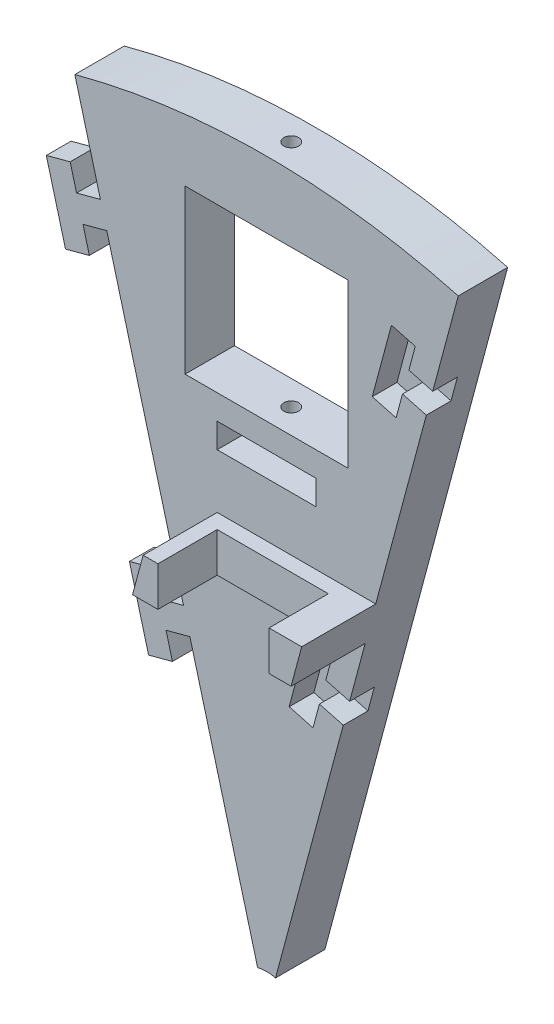
SolidWorks part; units mm, degrees
ref_plane "Front Plane" through (0, 0, 0) normal (0, 0, 1) x (1, 0, 0)
ref_plane "Top Plane" through (0, 0, 0) normal (0, 1, 0) x (1, 0, 0)
ref_plane "Right Plane" through (0, 0, 0) normal (1, 0, 0) x (0, 0, -1)
sketch "Sketch1" plane through (0, 0, 0) normal (0, 0, 1) x (1, 0, 0)
  line L0 (0, 0) -> (103.5, 0) construction
  line L1 (37.4606, 97.8836) -> (66.0394, 81.3836)
  line L2 (-16.5, 103.5) -> (16.5, 103.5)
  line L3 (-16.5, 103.5) -> (-16.5, 136.5)
  line L4 (-16.5, 136.5) -> (16.5, 136.5)
  line L5 (16.5, 103.5) -> (16.5, 136.5)
  line L6 (-16.5, 103.5) -> (16.5, 136.5) construction
  line L7 (-16.5, 136.5) -> (16.5, 103.5) construction
  line L8 (37.4606, 97.8836) -> (53.9606, 126.4625)
  line L9 (53.9606, 126.4625) -> (82.5394, 109.9625)
  line L10 (66.0394, 81.3836) -> (82.5394, 109.9625)
  line L11 (81.3836, 66.0394) -> (97.8836, 37.4606)
  line L12 (81.3836, 66.0394) -> (109.9625, 82.5394)
  line L13 (109.9625, 82.5394) -> (126.4625, 53.9606)
  line L14 (97.8836, 37.4606) -> (126.4625, 53.9606)
  line L15 (103.5, 16.5) -> (103.5, -16.5)
  line L16 (103.5, 16.5) -> (136.5, 16.5)
  line L17 (136.5, 16.5) -> (136.5, -16.5)
  line L18 (103.5, -16.5) -> (136.5, -16.5)
  line L19 (97.8836, -37.4606) -> (81.3836, -66.0394)
  line L20 (97.8836, -37.4606) -> (126.4625, -53.9606)
  line L21 (126.4625, -53.9606) -> (109.9625, -82.5394)
  line L22 (81.3836, -66.0394) -> (109.9625, -82.5394)
  line L23 (66.0394, -81.3836) -> (37.4606, -97.8836)
  line L24 (66.0394, -81.3836) -> (82.5394, -109.9625)
  line L25 (82.5394, -109.9625) -> (53.9606, -126.4625)
  line L26 (37.4606, -97.8836) -> (53.9606, -126.4625)
  line L27 (16.5, -103.5) -> (-16.5, -103.5)
  line L28 (16.5, -103.5) -> (16.5, -136.5)
  line L29 (16.5, -136.5) -> (-16.5, -136.5)
  line L30 (-16.5, -103.5) -> (-16.5, -136.5)
  line L31 (-37.4606, -97.8836) -> (-66.0394, -81.3836)
  line L32 (-37.4606, -97.8836) -> (-53.9606, -126.4625)
  line L33 (-53.9606, -126.4625) -> (-82.5394, -109.9625)
  line L34 (-66.0394, -81.3836) -> (-82.5394, -109.9625)
  line L35 (-81.3836, -66.0394) -> (-97.8836, -37.4606)
  line L36 (-81.3836, -66.0394) -> (-109.9625, -82.5394)
  line L37 (-109.9625, -82.5394) -> (-126.4625, -53.9606)
  line L38 (-97.8836, -37.4606) -> (-126.4625, -53.9606)
  line L39 (-103.5, -16.5) -> (-103.5, 16.5)
  line L40 (-103.5, -16.5) -> (-136.5, -16.5)
  line L41 (-136.5, -16.5) -> (-136.5, 16.5)
  line L42 (-103.5, 16.5) -> (-136.5, 16.5)
  line L43 (-97.8836, 37.4606) -> (-81.3836, 66.0394)
  line L44 (-97.8836, 37.4606) -> (-126.4625, 53.9606)
  line L45 (-126.4625, 53.9606) -> (-109.9625, 82.5394)
  line L46 (-81.3836, 66.0394) -> (-109.9625, 82.5394)
  line L47 (-66.0394, 81.3836) -> (-37.4606, 97.8836)
  line L48 (-66.0394, 81.3836) -> (-82.5394, 109.9625)
  line L49 (-82.5394, 109.9625) -> (-53.9606, 126.4625)
  line L50 (-37.4606, 97.8836) -> (-53.9606, 126.4625)
  line L51 (0, 103.5) -> (0, 0) construction
  line L52 (0, 0) -> (0, -103.5) construction
  circle A0 centre (0, 0) radius 150
  point P4 (0, 120)
  point P56 (0, 0)
  dimension "D1" = 300
  dimension "D2" = 33
  dimension "D3" = 120
  dimension "D4" = 12
extrude "Boss-Extrude1" add sketch "Sketch1" along normal mid plane 10
ref_plane "Plane1" through (0, -150, 0) normal (0, -1, 0) x (-1, 0, 0)
sketch "Sketch4" plane through (0, -150, 0) normal (0, -1, 0) x (-1, 0, 0)
  circle A0 centre (0, 0) radius 1.5
  dimension "D1" = 3
extrude "Cut-Extrude1" cut sketch "Sketch4" against normal blind 55
pattern_circular "CirPattern1" count 12 every 30 about axis through (0, 0, 5) along (0, 0, -1) of "Cut-Extrude1" reverse direction yes
sketch "Sketch5" plane through (0, 0, -5) normal (0, 0, -1) x (-1, 0, 0)
  line L0 (0, 0) -> (0, 116.0721) construction
  line L1 (38.0897, 85.9734) -> (55.4103, 75.9734)
  line L2 (-10, 93.5) -> (10, 93.5)
  line L3 (-10, 93.5) -> (-10, 98.5)
  line L4 (-10, 98.5) -> (10, 98.5)
  line L5 (10, 93.5) -> (10, 98.5)
  line L6 (-10, 93.5) -> (10, 98.5) construction
  line L7 (-10, 98.5) -> (10, 93.5) construction
  line L8 (16.5, 103.5) -> (-16.5, 103.5) construction
  line L9 (38.0897, 85.9734) -> (40.5897, 90.3035)
  line L10 (40.5897, 90.3035) -> (57.9103, 80.3035)
  line L11 (55.4103, 75.9734) -> (57.9103, 80.3035)
  line L12 (75.9734, 55.4103) -> (85.9734, 38.0897)
  line L13 (75.9734, 55.4103) -> (80.3035, 57.9103)
  line L14 (80.3035, 57.9103) -> (90.3035, 40.5897)
  line L15 (85.9734, 38.0897) -> (90.3035, 40.5897)
  line L16 (93.5, 10) -> (93.5, -10)
  line L17 (93.5, 10) -> (98.5, 10)
  line L18 (98.5, 10) -> (98.5, -10)
  line L19 (93.5, -10) -> (98.5, -10)
  line L20 (85.9734, -38.0897) -> (75.9734, -55.4103)
  line L21 (85.9734, -38.0897) -> (90.3035, -40.5897)
  line L22 (90.3035, -40.5897) -> (80.3035, -57.9103)
  line L23 (75.9734, -55.4103) -> (80.3035, -57.9103)
  line L24 (55.4103, -75.9734) -> (38.0897, -85.9734)
  line L25 (55.4103, -75.9734) -> (57.9103, -80.3035)
  line L26 (57.9103, -80.3035) -> (40.5897, -90.3035)
  line L27 (38.0897, -85.9734) -> (40.5897, -90.3035)
  line L28 (10, -93.5) -> (-10, -93.5)
  line L29 (10, -93.5) -> (10, -98.5)
  line L30 (10, -98.5) -> (-10, -98.5)
  line L31 (-10, -93.5) -> (-10, -98.5)
  line L32 (-38.0897, -85.9734) -> (-55.4103, -75.9734)
  line L33 (-38.0897, -85.9734) -> (-40.5897, -90.3035)
  line L34 (-40.5897, -90.3035) -> (-57.9103, -80.3035)
  line L35 (-55.4103, -75.9734) -> (-57.9103, -80.3035)
  line L36 (-75.9734, -55.4103) -> (-85.9734, -38.0897)
  line L37 (-75.9734, -55.4103) -> (-80.3035, -57.9103)
  line L38 (-80.3035, -57.9103) -> (-90.3035, -40.5897)
  line L39 (-85.9734, -38.0897) -> (-90.3035, -40.5897)
  line L40 (-93.5, -10) -> (-93.5, 10)
  line L41 (-93.5, -10) -> (-98.5, -10)
  line L42 (-98.5, -10) -> (-98.5, 10)
  line L43 (-93.5, 10) -> (-98.5, 10)
  line L44 (-85.9734, 38.0897) -> (-75.9734, 55.4103)
  line L45 (-85.9734, 38.0897) -> (-90.3035, 40.5897)
  line L46 (-90.3035, 40.5897) -> (-80.3035, 57.9103)
  line L47 (-75.9734, 55.4103) -> (-80.3035, 57.9103)
  line L48 (-55.4103, 75.9734) -> (-38.0897, 85.9734)
  line L49 (-55.4103, 75.9734) -> (-57.9103, 80.3035)
  line L50 (-57.9103, 80.3035) -> (-40.5897, 90.3035)
  line L51 (-38.0897, 85.9734) -> (-40.5897, 90.3035)
  line L52 (-103.5, 16.5) -> (-103.5, -16.5) construction
  line L53 (-16.5, -103.5) -> (16.5, -103.5) construction
  point P1 (0, 96)
  point P57 (0, 0)
  dimension "D1" = 5
  dimension "D2" = 20
  dimension "D3" = 5
  dimension "D5" = 5
  dimension "D6" = 5
  dimension "D4" = 12
extrude "Cut-Extrude2" cut sketch "Sketch5" against normal up to next
sketch "Sketch6" plane through (0, 0, 5) normal (0, 0, 1) x (1, 0, 0)
  line L0 (0, 0) -> (-38.8229, 144.8889)
  line L1 (0, 0) -> (38.8229, 144.8889)
  line L2 (0, 175.6379) -> (0, 153.992) construction
  line L3 (-38.8229, 144.8889) -> (0, 144.8889)
  line L4 (0, 144.8889) -> (38.8229, 144.8889)
  circle A0 centre (0, 0) radius 150 construction
  arc A1 (-1.8117, 6.7615) -> (1.8117, 6.7615) centre (0, 0) cw
  circle A2 centre (0, 0) radius 150
  dimension "D2" = 7
  dimension "D1" = 30
extrude "Cut-Extrude3" cut sketch "Sketch6" against normal blind 10 contours L2 L0 A2 | L1 L2 A2 | A1 L2 L1 | L2 A1 L0 region at (0, -8.9874, 5) region at (0, 4.6135, 5)
sketch "Sketch7" plane through (0, 0, 5) normal (0, 0, 1) x (1, 0, 0)
  line L0 (-24.5878, 91.763) -> (-39.0277, 87.8938) construction
  line L1 (-1.8117, 6.7615) -> (-38.8229, 144.8889) construction
  line L2 (-1.8117, 6.7615) -> (-38.8229, 144.8889)
  line L3 (-35.8879, 114.617) -> (-37.182, 119.4466)
  line L4 (-37.182, 119.4466) -> (-32.3524, 120.7407)
  line L5 (30.0564, 131.7087) -> (25.2268, 133.0028)
  line L6 (25.2268, 133.0028) -> (21.3445, 118.5139)
  line L7 (28.7623, 126.8791) -> (30.0564, 131.7087)
  line L8 (-33.6465, 125.5704) -> (-38.4761, 124.2763)
  line L9 (-38.4761, 124.2763) -> (-39.7702, 129.1059)
  line L10 (-39.7702, 129.1059) -> (-44.5998, 127.8118)
  line L11 (-44.5998, 127.8118) -> (-40.7175, 113.3229)
  line L12 (33.5919, 125.585) -> (28.7623, 126.8791)
  line L13 (26.1741, 117.2198) -> (27.4682, 122.0494)
  line L14 (-40.7175, 113.3229) -> (-35.8879, 114.617)
  line L15 (21.3445, 118.5139) -> (26.1741, 117.2198)
  line L16 (27.4682, 122.0494) -> (32.2978, 120.7553)
  line L17 (0, 0.1091) -> (-35.8879, 114.617) construction
  line L18 (0, 0.1091) -> (26.1741, 117.2198) construction
  line L19 (-27.7766, 65.0266) -> (-22.947, 66.3207)
  line L20 (-22.947, 66.3207) -> (-21.6529, 61.4911)
  line L21 (-21.6529, 61.4911) -> (-16.8232, 62.7852)
  line L22 (-15.5291, 57.9555) -> (-20.3588, 56.6615)
  line L23 (-23.8943, 50.5377) -> (-27.7766, 65.0266)
  line L24 (-20.3588, 56.6615) -> (-19.0647, 51.8318)
  line L25 (-19.0647, 51.8318) -> (-23.8943, 50.5377)
  line L26 (8.4854, 70.3048) -> (13.315, 69.0107)
  line L27 (4.6031, 55.8159) -> (8.4854, 70.3048)
  line L28 (13.315, 69.0107) -> (12.0209, 64.1811)
  line L29 (12.0209, 64.1811) -> (16.8505, 62.887)
  line L30 (15.5564, 58.0574) -> (10.7268, 59.3514)
  line L31 (10.7268, 59.3514) -> (9.4327, 54.5218)
  line L32 (9.4327, 54.5218) -> (4.6031, 55.8159)
  line L33 (1.8117, 6.7615) -> (38.8229, 144.8889) construction
  point P7 (-38.3027, 113.97)
  point P44 (0.2036, 0)
  point P47 (0.2036, 0)
  line M9 (-38.8229, 144.8889) -> (-1.8117, 6.7615)
  dimension "D1" = 5
  dimension "D2" = 90
  dimension "D3" = 5
  dimension "D4" = 5
  dimension "D5" = 20
  dimension "D6" = 15
  dimension "D7" = 5
  dimension "D8" = 5
  dimension "D9" = 90
  dimension "D11" = 30
  dimension "D12" = 20
  dimension "D13" = 120
  dimension "D14" = 30
  dimension "D17" = 60
  dimension "D18" = 10
  dimension "D10" = 2
  dimension "D15" = 2
  dimension "D16" = 2
extrude "Boss-Extrude2" add sketch "Sketch7" against normal blind 5 contours L25 L24 L22 L21 L20 L19 L23 M9 | L11 L14 L3 L4 L2 L8 L9 L10 region at (-22.2132, 58.7527, 5) region at (-39.0365, 121.5379, 5)
sketch "Sketch9" plane through (0, 0, 5) normal (0, 0, 1) x (1, 0, 0)
  line L0 (-15.5291, 57.9555) -> (-20.3588, 56.6615) construction
  line L1 (-20.3588, 56.6615) -> (-19.0647, 51.8318) construction
  line L2 (-19.0647, 51.8318) -> (-23.8943, 50.5377) construction
  line L3 (-23.8943, 50.5377) -> (-27.7766, 65.0266) construction
  line L4 (-27.7766, 65.0266) -> (-22.947, 66.3207) construction
  line L5 (-21.6529, 61.4911) -> (-16.8232, 62.7852) construction
  line L6 (-37.182, 119.4466) -> (-32.3524, 120.7407) construction
  line L7 (-35.8879, 114.617) -> (-37.182, 119.4466) construction
  line L8 (-40.7175, 113.3229) -> (-35.8879, 114.617) construction
  line L9 (-44.5998, 127.8118) -> (-40.7175, 113.3229) construction
  line L10 (-39.7702, 129.1059) -> (-44.5998, 127.8118) construction
  line L11 (-38.4761, 124.2763) -> (-39.7702, 129.1059) construction
  line L12 (-33.6465, 125.5704) -> (-38.4761, 124.2763) construction
  line L13 (-15.5291, 57.9555) -> (-20.3588, 56.6615)
  line L14 (-20.3588, 56.6615) -> (-19.0647, 51.8318)
  line L15 (-19.0647, 51.8318) -> (-23.8943, 50.5377)
  line L16 (-23.8943, 50.5377) -> (-27.7766, 65.0266)
  line L17 (-27.7766, 65.0266) -> (-22.947, 66.3207)
  line L18 (-21.6529, 61.4911) -> (-16.8232, 62.7852)
  line L19 (-37.182, 119.4466) -> (-32.3524, 120.7407)
  line L20 (-35.8879, 114.617) -> (-37.182, 119.4466)
  line L21 (-40.7175, 113.3229) -> (-35.8879, 114.617)
  line L22 (-44.5998, 127.8118) -> (-40.7175, 113.3229)
  line L23 (-39.7702, 129.1059) -> (-44.5998, 127.8118)
  line L24 (-38.4761, 124.2763) -> (-39.7702, 129.1059)
  line L25 (-33.6465, 125.5704) -> (-38.4761, 124.2763)
  line L26 (33.6465, 125.5704) -> (28.8168, 126.8645)
  line L27 (30.1109, 131.6941) -> (25.2813, 132.9882)
  line L28 (27.5228, 122.0348) -> (32.3524, 120.7407)
  line L29 (26.2287, 117.2052) -> (27.5228, 122.0348)
  line L30 (21.399, 118.4993) -> (26.2287, 117.2052)
  line L31 (25.2813, 132.9882) -> (21.399, 118.4993)
  line L32 (28.8168, 126.8645) -> (30.1109, 131.6941)
  line L33 (15.5291, 57.9555) -> (10.6995, 59.2496)
  line L34 (10.6995, 59.2496) -> (9.4054, 54.42)
  line L35 (9.4054, 54.42) -> (4.5758, 55.7141)
  line L36 (4.5758, 55.7141) -> (8.4581, 70.203)
  line L37 (11.9936, 64.0793) -> (16.8232, 62.7852)
  line L38 (8.4581, 70.203) -> (13.2877, 68.9089)
  line L39 (0, 0) -> (-19.0647, 51.8318) construction
  line L40 (0, 0) -> (9.4054, 54.42) construction
  line L41 (-22.947, 66.3207) -> (-21.6529, 61.4911) construction
  line L42 (-22.947, 66.3207) -> (-21.6529, 61.4911)
  line L43 (13.2877, 68.9089) -> (11.9936, 64.0793)
  point P39 (0, 0)
  line M5 (1.8117, 6.7615) -> (38.8229, 144.8889)
  dimension "D2" = 30
  dimension "D1" = 2
  dimension "D3" = 2
extrude "Cut-Extrude4" cut sketch "Sketch9" against normal blind 5 contours L43 L38 L36 L35 L34 L33 L37 M5 | L26 L32 L27 L31 L30 L29 L28 M5 region at (26.9624, 124.7732, 5) region at (10.1392, 61.988, 5)
sketch "Sketch10" plane through (0, 0, 5) normal (0, 0, 1) x (1, 0, 0)
  line L0 (-10, 93.5) -> (-10, 98.5) construction
  line L1 (-10, 82.5) -> (-7, 82.5)
  line L3 (-10, 74.5) -> (-7, 74.5)
  line L4 (-7, 82.5) -> (-7, 74.5)
  line L5 (-10, 82.5) -> (-12.1436, 74.5)
  line L6 (-12.1436, 74.5) -> (-10, 74.5)
  line L7 (10, 93.5) -> (-10, 93.5) construction
  line L8 (16.8232, 62.7852) -> (32.3524, 120.7407) construction
  line L9 (15.5, 82.5) -> (22.1058, 82.5)
  line L10 (15.5, 82.5) -> (15.5, 74.5)
  line L11 (15.5, 74.5) -> (19.9622, 74.5)
  line L12 (22.1058, 82.5) -> (19.9622, 74.5)
  line L13 (16.8232, 62.7852) -> (32.3524, 120.7407)
  point P15 (0, 0)
  line M19 (16.8232, 62.7852) -> (32.3524, 120.7407)
  dimension "D1" = 3
  dimension "D2" = 11
  dimension "D3" = 22.5
  dimension "D4" = 3
  dimension "D5" = 8
  dimension "D6" = 8
  dimension "D7" = 75
extrude "Boss-Extrude3" add sketch "Sketch10" along normal blind 15 contours L4 L1 L3 | L10 L11 L9 M19 region at (-9.0829, 78.149, 5) region at (18.3016, 78.7582, 5)
sketch "Sketch11" plane through (0, 0, 5) normal (0, 0, 1) x (1, 0, 0)
  line L0 (-7, 82.5) -> (-7, 74.5) construction
  line L1 (-7, 82.5) -> (-7, 74.5)
  line L3 (-7, 82.5) -> (15.5, 82.5)
  line L4 (-7, 82.5) -> (-7, 74.5)
  line L5 (-7, 74.5) -> (15.5, 74.5)
  line L6 (15.5, 82.5) -> (15.5, 74.5)
  line L38 (16.8232, 62.7852) -> (19.9622, 74.5)
  line L39 (19.9622, 74.5) -> (15.5, 74.5)
  line L40 (15.5, 74.5) -> (15.5, 82.5)
  line L41 (15.5, 82.5) -> (22.1058, 82.5)
  line L42 (22.1058, 82.5) -> (32.3524, 120.7407)
  line L43 (32.3524, 120.7407) -> (27.5228, 122.0348)
  line L44 (27.5228, 122.0348) -> (26.2287, 117.2052)
  line L45 (26.2287, 117.2052) -> (21.399, 118.4993)
  line L46 (21.399, 118.4993) -> (25.2813, 132.9882)
  line L47 (25.2813, 132.9882) -> (30.1109, 131.6941)
  line L48 (30.1109, 131.6941) -> (28.8168, 126.8645)
  line L49 (28.8168, 126.8645) -> (33.6465, 125.5704)
  line L50 (33.6465, 125.5704) -> (38.8229, 144.8889)
  line L51 (-38.8229, 144.8889) -> (-33.6465, 125.5704)
  line L52 (-33.6465, 125.5704) -> (-38.4761, 124.2763)
  line L53 (-38.4761, 124.2763) -> (-39.7702, 129.1059)
  line L54 (-39.7702, 129.1059) -> (-44.5998, 127.8118)
  line L55 (-44.5998, 127.8118) -> (-40.7175, 113.3229)
  line L56 (-40.7175, 113.3229) -> (-35.8879, 114.617)
  line L57 (-35.8879, 114.617) -> (-37.182, 119.4466)
  line L58 (-37.182, 119.4466) -> (-32.3524, 120.7407)
  line L59 (-32.3524, 120.7407) -> (-16.8232, 62.7852)
  line L60 (-16.8232, 62.7852) -> (-21.6529, 61.4911)
  line L61 (-21.6529, 61.4911) -> (-22.947, 66.3207)
  line L62 (-22.947, 66.3207) -> (-27.7766, 65.0266)
  line L63 (-27.7766, 65.0266) -> (-23.8943, 50.5377)
  line L64 (-23.8943, 50.5377) -> (-19.0647, 51.8318)
  line L65 (-19.0647, 51.8318) -> (-20.3588, 56.6615)
  line L66 (-20.3588, 56.6615) -> (-15.5291, 57.9555)
  line L67 (-15.5291, 57.9555) -> (-1.8117, 6.7615)
  line L68 (1.8117, 6.7615) -> (15.5291, 57.9555)
  line L69 (15.5291, 57.9555) -> (10.6995, 59.2496)
  line L70 (10.6995, 59.2496) -> (9.4054, 54.42)
  line L71 (9.4054, 54.42) -> (4.5758, 55.7141)
  line L72 (4.5758, 55.7141) -> (8.4581, 70.203)
  line L73 (8.4581, 70.203) -> (13.2877, 68.9089)
  line L74 (13.2877, 68.9089) -> (11.9936, 64.0793)
  line L75 (11.9936, 64.0793) -> (16.8232, 62.7852)
  line L76 (16.8232, 62.7852) -> (19.9622, 74.5)
  line L77 (19.9622, 74.5) -> (15.5, 74.5)
  line L78 (15.5, 74.5) -> (15.5, 82.5)
  line L79 (15.5, 82.5) -> (22.1058, 82.5)
  line L80 (22.1058, 82.5) -> (32.3524, 120.7407)
  line L81 (32.3524, 120.7407) -> (27.5228, 122.0348)
  line L82 (27.5228, 122.0348) -> (26.2287, 117.2052)
  line L83 (26.2287, 117.2052) -> (21.399, 118.4993)
  line L84 (21.399, 118.4993) -> (25.2813, 132.9882)
  line L85 (25.2813, 132.9882) -> (30.1109, 131.6941)
  line L86 (30.1109, 131.6941) -> (28.8168, 126.8645)
  line L87 (28.8168, 126.8645) -> (33.6465, 125.5704)
  line L88 (33.6465, 125.5704) -> (38.8229, 144.8889)
  line L89 (-38.8229, 144.8889) -> (-33.6465, 125.5704)
  line L90 (-33.6465, 125.5704) -> (-38.4761, 124.2763)
  line L91 (-38.4761, 124.2763) -> (-39.7702, 129.1059)
  line L92 (-39.7702, 129.1059) -> (-44.5998, 127.8118)
  line L93 (-44.5998, 127.8118) -> (-40.7175, 113.3229)
  line L94 (-40.7175, 113.3229) -> (-35.8879, 114.617)
  line L95 (-35.8879, 114.617) -> (-37.182, 119.4466)
  line L96 (-37.182, 119.4466) -> (-32.3524, 120.7407)
  line L97 (-32.3524, 120.7407) -> (-16.8232, 62.7852)
  line L98 (-16.8232, 62.7852) -> (-21.6529, 61.4911)
  line L99 (-21.6529, 61.4911) -> (-22.947, 66.3207)
  line L100 (-22.947, 66.3207) -> (-27.7766, 65.0266)
  line L101 (-27.7766, 65.0266) -> (-23.8943, 50.5377)
  line L102 (-23.8943, 50.5377) -> (-19.0647, 51.8318)
  line L103 (-19.0647, 51.8318) -> (-20.3588, 56.6615)
  line L104 (-20.3588, 56.6615) -> (-15.5291, 57.9555)
  line L105 (-15.5291, 57.9555) -> (-1.8117, 6.7615)
  line L106 (1.8117, 6.7615) -> (15.5291, 57.9555)
  line L107 (15.5291, 57.9555) -> (10.6995, 59.2496)
  line L108 (10.6995, 59.2496) -> (9.4054, 54.42)
  line L109 (9.4054, 54.42) -> (4.5758, 55.7141)
  line L110 (4.5758, 55.7141) -> (8.4581, 70.203)
  line L111 (8.4581, 70.203) -> (13.2877, 68.9089)
  line L112 (13.2877, 68.9089) -> (11.9936, 64.0793)
  line L113 (11.9936, 64.0793) -> (16.8232, 62.7852)
  arc A2 (38.8229, 144.8889) -> (-38.8229, 144.8889) centre (0, 0) ccw
  arc A3 (1.8117, 6.7615) -> (-1.8117, 6.7615) centre (0, 0) ccw
  arc A4 (38.8229, 144.8889) -> (-38.8229, 144.8889) centre (0, 0) ccw
  arc A5 (1.8117, 6.7615) -> (-1.8117, 6.7615) centre (0, 0) ccw
  dimension "D1" = 0
extrude "Boss-Extrude4" add sketch "Sketch11" along normal blind 3 contours L6 L3 L1 L5 region at (4.25, 78.5, 5)
